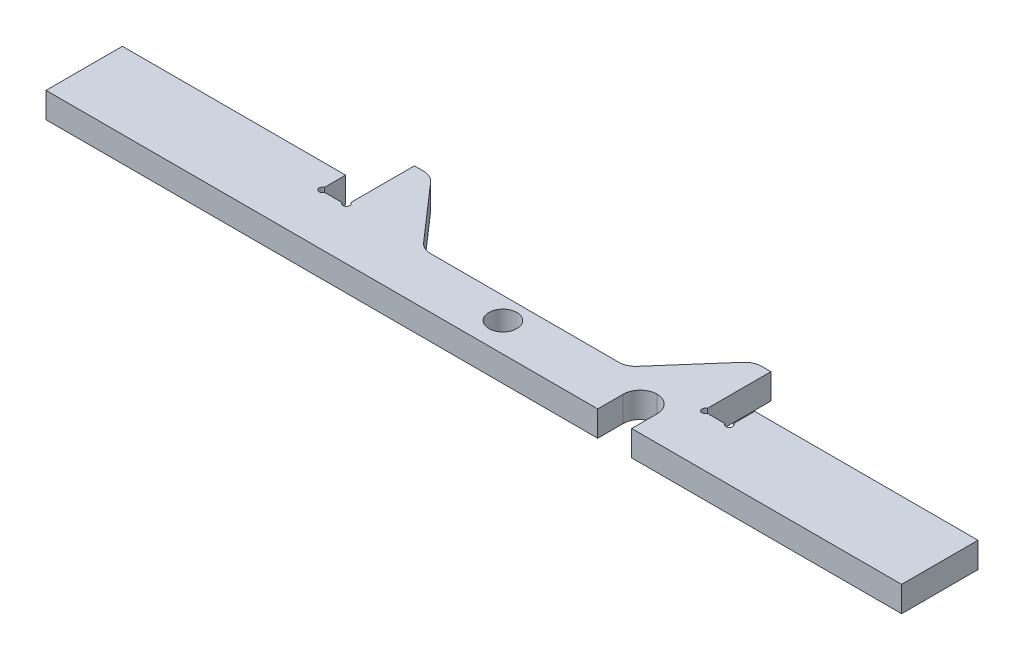
SolidWorks part; units mm, degrees
material "S355J2H"
ref_plane "Front Plane" through (0, 0, 0) normal (0, 0, 1) x (1, 0, 0)
ref_plane "Top Plane" through (0, 0, 0) normal (0, 1, 0) x (1, 0, 0)
ref_plane "Right Plane" through (0, 0, 0) normal (1, 0, 0) x (0, 0, -1)
sketch "Sketch1" plane through (0, 0, 0) normal (0, 1, 0) x (1, 0, 0)
  line L0 (-105, 0) -> (105, 0)
  line L1 (-105, 0) -> (-105, 70)
  line L2 (0, 17.15) -> (0, 0) construction
  line L3 (0, 17.15) -> (0, 58.75) construction
  line L4 (-105, 70) -> (-95, 70)
  line L7 (105, 0) -> (105, 70)
  line L8 (105, 70) -> (95, 70)
  line L9 (60, 30) -> (-60, 30)
  line L12 (60, 30) -> (95, 70)
  line L15 (-60, 30) -> (-95, 70)
  circle A0 centre (0, 17.15) radius 8.25
  dimension "D3" = 16.5
  dimension "D4" = 30
  dimension "D1" = 210
  dimension "D2" = 17.15
  dimension "D6" = 70
  dimension "D7" = 10
  dimension "D8" = 120
extrude "Boss-Extrude1" add sketch "Sketch1" along normal blind 15
fillet "Fillet1" radius 10 4 edges at (-95, 7.5, -70) (95, 7.5, -70) (-60, 7.5, -30) (60, 7.5, -30)
sketch "Sketch2" plane through (0, 15, 0) normal (0, 1, 0) x (1, 0, 0)
  line L0 (105, 0) -> (252, 0)
  line L1 (252, 0) -> (252, 45)
  line L2 (252, 45) -> (120.5, 45)
  line L3 (120.5, 45) -> (120.5, 30)
  line L4 (120.5, 30) -> (105, 30)
  line L5 (105, 0) -> (105, 70) construction
  line L6 (105, 30) -> (105, 0)
  line L7 (55.4623, 30) -> (-55.4623, 30) construction
  line L8 (105, 70) -> (99.5377, 70) construction
  dimension "D1" = 15.5
  dimension "D2" = 147
  dimension "D3" = 25
extrude "Boss-Extrude2" add sketch "Sketch2" against normal up to surface (15 mm away) up to face at (0, 0, -45)
mirror "Mirror1" about plane through (0, 0, 0) normal (1, 0, 0) of "Boss-Extrude2"
sketch "Sketch3" plane through (0, 15, 0) normal (0, 1, 0) x (1, 0, 0)
  line L0 (-252, 0) -> (252, 0) construction
  line L1 (93, 0) -> (73, 0)
  line L2 (93, 0) -> (93, 25)
  line L3 (93, 25) -> (73, 25)
  line L4 (73, 0) -> (73, 25)
  line L5 (105, 30) -> (105, 70) construction
  dimension "D1" = 12
  dimension "D2" = 25
  dimension "D3" = 20
extrude "Cut-Extrude1" cut sketch "Sketch3" against normal through all
fillet "Fillet2" radius 10 2 edges at (73, 7.5, -25) (93, 7.5, -25)
sketch "Sketch4" plane through (0, 15, 0) normal (0, 1, 0) x (1, 0, 0)
  line L0 (-119.7929, 30.7071) -> (-120.5, 30) construction
  line L1 (-120.5, 45) -> (-120.5, 30) construction
  line L2 (-112.75, 30) -> (-112.75, 41.3057) construction
  line L3 (-120.5, 30) -> (-105, 30) construction
  line L4 (-105.7071, 30.7071) -> (-105, 30) construction
  line L5 (0, 0) -> (0, 77.0648) construction
  line L6 (105.7071, 30.7071) -> (105, 30) construction
  line L7 (112.75, 30) -> (112.75, 41.3057) construction
  line L8 (119.7929, 30.7071) -> (120.5, 30) construction
  circle A0 centre (-119.7929, 30.7071) radius 2
  circle A1 centre (-105.7071, 30.7071) radius 2
  circle A2 centre (105.7071, 30.7071) radius 2
  circle A3 centre (119.7929, 30.7071) radius 2
  dimension "D2" = 4
  dimension "D1" = 1
  dimension "D3" = 45
extrude "Cut-Extrude2" cut sketch "Sketch4" against normal through all
